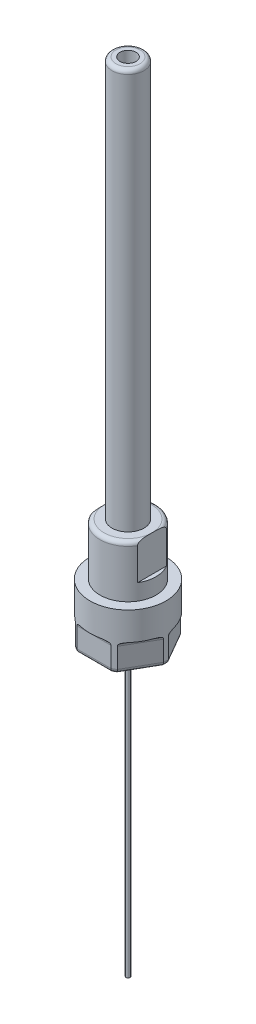
SolidWorks part; units mm, degrees
ref_plane "Front" through (0, 0, 0) normal (0, 0, 1) x (1, 0, 0)
ref_plane "Top" through (0, 0, 0) normal (0, 1, 0) x (1, 0, 0)
ref_plane "Right" through (0, 0, 0) normal (1, 0, 0) x (0, 0, -1)
sketch "Esquisse1" plane through (0, 0, 0) normal (0, 0, 1) x (1, 0, 0)
  line L0 (0, 0) -> (0, 127) construction
  line L1 (4, 127) -> (4, 27)
  line L2 (4, 27) -> (7, 27)
  line L3 (7, 27) -> (7, 14)
  line L4 (7, 14) -> (9.5, 14)
  line L5 (9.5, 14) -> (9.5, 0)
  line L6 (9.5, 0) -> (0, 0)
  line L7 (4, 127) -> (2, 127)
  line L8 (2, 127) -> (2, 123)
  line L9 (2, 123) -> (0, 121)
  line L10 (0, 0) -> (0, 121)
  dimension "D1" = 8
  dimension "D2" = 19
  dimension "D3" = 14
  dimension "D4" = 14
  dimension "D5" = 13
  dimension "D6" = 100
  dimension "D7" = 4
  dimension "D8" = 4
  dimension "D9" = 45
revolve "Révolution1" add sketch "Esquisse1" angle 360 about L0
sketch "Esquisse2" plane through (0, 0, 0) normal (0, -1, 0) x (1, 0, 0)
  circle A0 centre (0, 0) radius 4
  dimension "D1" = 8
extrude "Enlèv. mat.-Extru.1" cut sketch "Esquisse2" against normal blind 8
sketch "Esquisse3" plane through (0, 27, 0) normal (0, 1, 0) x (1, 0, 0)
  line L0 (0, 0) -> (0, 3.3999) construction
  line L1 (6, -3.6056) -> (6, 3.6056)
  line L2 (-6, -3.6056) -> (-6, 3.6056)
  arc A0 (6, 3.6056) -> (6, -3.6056) centre (0, 0) cw
  circle A1 centre (0, 0) radius 7 construction
  arc A2 (-6, 3.6056) -> (-6, -3.6056) centre (0, 0) ccw
  dimension "D1" = 12
extrude "Enlèv. mat.-Extru.2" cut sketch "Esquisse3" against normal blind 9
sketch "Esquisse4" plane through (0, 0, 0) normal (0, -1, 0) x (1, 0, 0)
  line L1 (9.815, 0) -> (4.9075, 8.5)
  line L2 (4.9075, 8.5) -> (-4.9075, 8.5)
  line L3 (-4.9075, 8.5) -> (-9.815, 0)
  line L4 (-9.815, 0) -> (-4.9075, -8.5)
  line L5 (-4.9075, -8.5) -> (4.9075, -8.5)
  line L6 (4.9075, -8.5) -> (9.815, 0)
  circle A0 centre (0, 0) radius 8.5 construction
  circle A1 centre (0, 0) radius 15
  dimension "D2" = 30
  dimension "D1" = 17
extrude "Enlèv. mat.-Extru.3" cut sketch "Esquisse4" against normal blind 7
fillet "Congé1" radius 1 22 edges at (0, 127, -4) (0, 27, 7) (0, 27, -7) (0, 0, -8.5) (-4.75, 0, -8.2272) (-7.3612, 0, -4.25) (-9.5, 0, 0) (-7.3612, 0, 4.25) (-4.75, 0, 8.2272) (0, 0, 8.5) (4.75, 0, 8.2272) (7.3612, 0, 4.25) (9.5, 0, 0) (7.3612, 0, -4.25) (4.75, 0, -8.2272) (0, 0, -4) (0, 7, 8.5) (7.3612, 7, 4.25) (7.3612, 7, -4.25) (0, 7, -8.5) (-7.3612, 7, -4.25) (-7.3612, 7, 4.25)
sketch "Esquisse5" plane through (0, 8, 0) normal (0, -1, 0) x (1, 0, 0)
  circle A0 centre (0, 0) radius 0.5
  dimension "D1" = 1
extrude "Boss.-Extru.1" add sketch "Esquisse5" along normal blind 80
